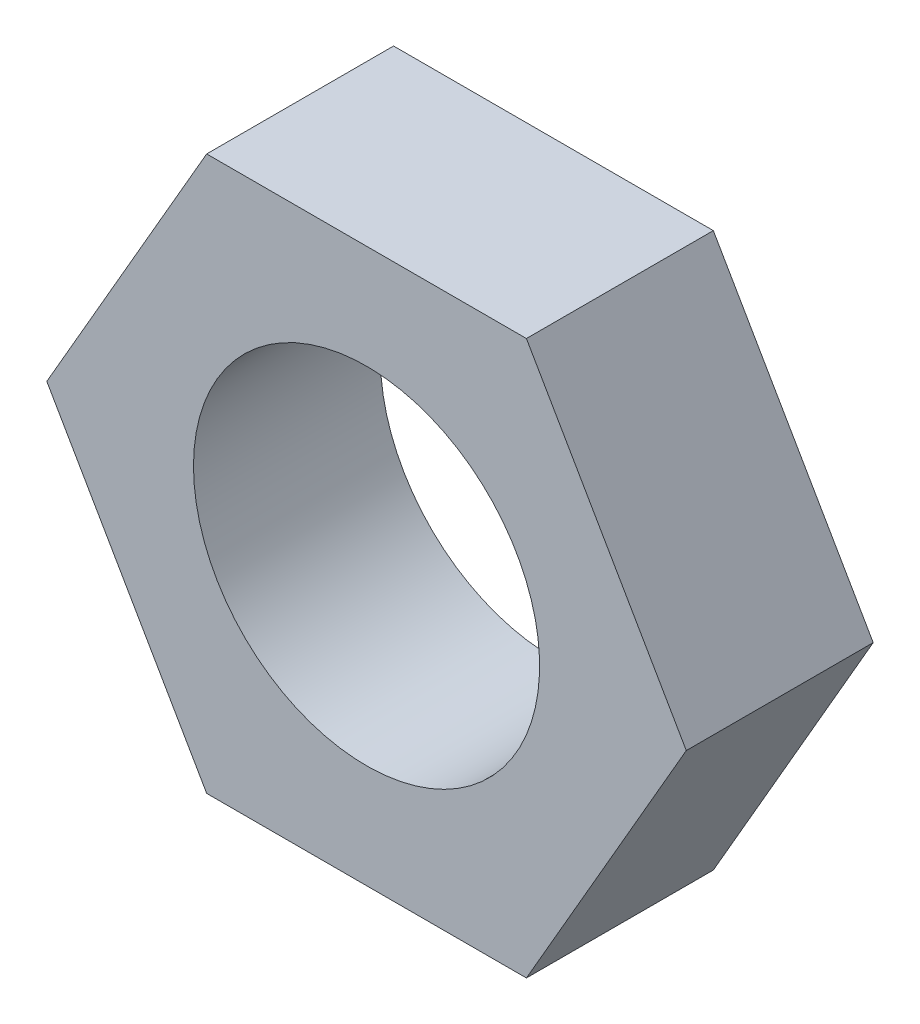
SolidWorks part; units mm, degrees
ref_plane "Front Plane" through (0, 0, 0) normal (0, 0, 1) x (1, 0, 0)
ref_plane "Top Plane" through (0, 0, 0) normal (0, 1, 0) x (1, 0, 0)
ref_plane "Right Plane" through (0, 0, 0) normal (1, 0, 0) x (0, 0, -1)
ref_plane "Plane1" through (0, 0, 2.7) normal (0, 0, 1) x (1, 0, 0)
sketch "Sketch1" plane through (0, 0, 2.7) normal (0, 0, 1) x (1, 0, 0)
  line L0 (-2.3094, 4) -> (-4.6188, 0)
  line L1 (-4.6188, 0) -> (-2.3094, -4)
  line L2 (-2.3094, -4) -> (2.3094, -4)
  line L3 (2.3094, -4) -> (4.6188, 0)
  line L4 (4.6188, 0) -> (2.3094, 4)
  line L5 (2.3094, 4) -> (-2.3094, 4)
  circle A0 centre (0, 0) radius 2.5
extrude "Boss-Extrude1" add sketch "Sketch1" against normal blind 2.7
ref_axis "Axis1" through (0, 0, 0) along (0, 0, 1)
